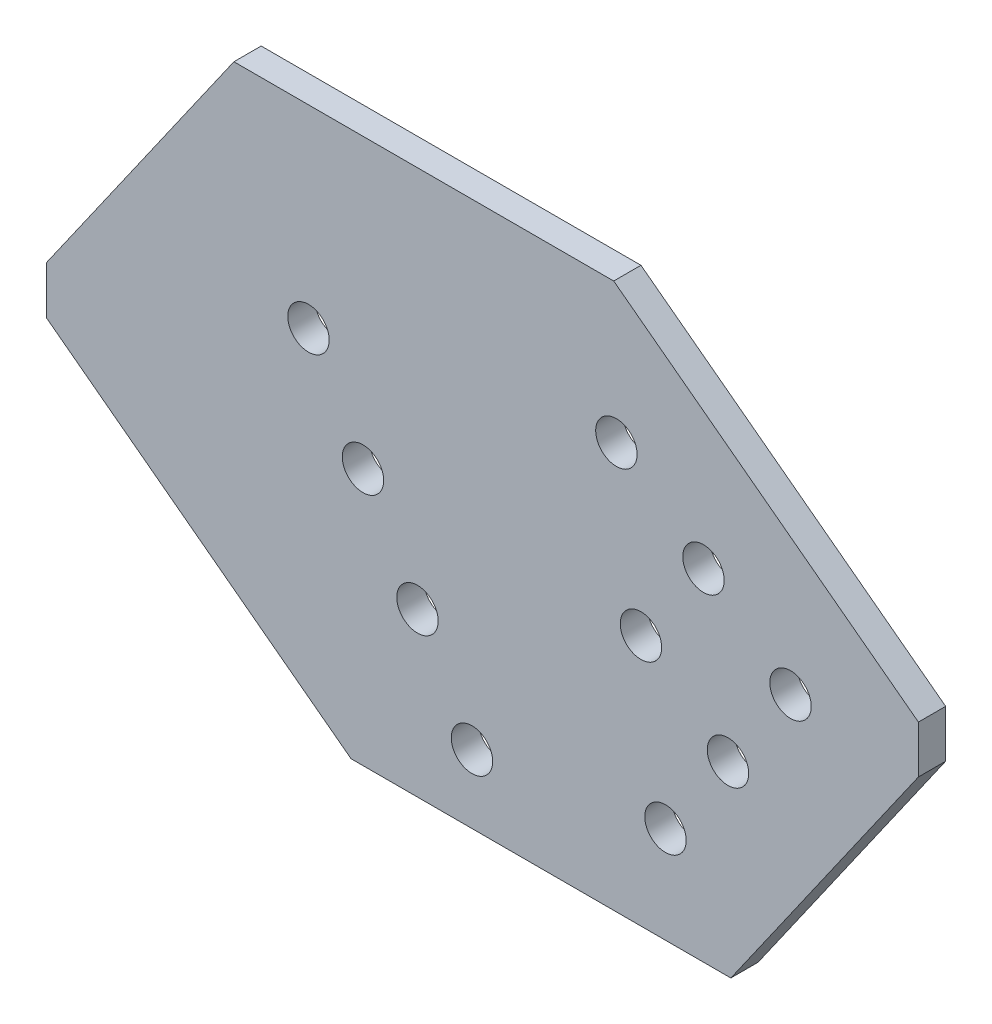
SolidWorks part; units mm, degrees
ref_plane "Front Plane" through (0, 0, 0) normal (0, 0, 1) x (1, 0, 0)
ref_plane "Top Plane" through (0, 0, 0) normal (0, 1, 0) x (1, 0, 0)
ref_plane "Right Plane" through (0, 0, 0) normal (1, 0, 0) x (0, 0, -1)
sketch "Sketch1" plane through (0, 0, 0) normal (0, 0, 1) x (1, 0, 0)
  line L1 (0, 0) -> (101.6, 0)
  line L2 (0, 0) -> (0, 63.5)
  line L3 (0, 63.5) -> (101.6, 63.5)
  line L4 (101.6, 0) -> (101.6, 63.5)
  dimension "D1" = 101.6
  dimension "D2" = 63.5
extrude "Boss-Extrude1" add sketch "Sketch1" along normal blind 3.175
sketch "Sketch2" plane through (0, 0, 3.175) normal (0, 0, 1) x (1, 0, 0)
  line L0 (101.6, 31.2097) -> (79.7467, 0)
  line L1 (101.6, 0) -> (101.6, 63.5) construction
  line L2 (0, 0) -> (101.6, 0) construction
  line L3 (101.6, 36.7493) -> (66.1007, 63.5)
  line L4 (101.6, 63.5) -> (0, 63.5) construction
  line L5 (66.1007, 63.5) -> (101.6, 63.5)
  line L6 (101.6, 63.5) -> (101.6, 36.7493)
  line L7 (101.6, 31.2097) -> (101.6, 0)
  line L8 (101.6, 0) -> (79.7467, 0)
  dimension "D1" = 55
  dimension "D2" = 37
  dimension "D3" = 38.1
  dimension "D4" = 44.45
extrude "Cut-Extrude1" cut sketch "Sketch2" against normal through all
sketch "Sketch3" plane through (0, 0, 3.175) normal (0, 0, 1) x (1, 0, 0)
  line L0 (21.8533, 63.5) -> (0, 32.2903)
  line L1 (66.1007, 63.5) -> (0, 63.5) construction
  line L2 (0, 63.5) -> (0, 0) construction
  line L3 (0, 32.2903) -> (0, 63.5)
  line L4 (0, 63.5) -> (21.8533, 63.5)
  line L5 (0, 0) -> (0, 26.7507)
  line L6 (0, 26.7507) -> (35.4993, 0)
  line L7 (0, 0) -> (79.7467, 0) construction
  line L8 (35.4993, 0) -> (0, 0)
  dimension "D1" = 55
  dimension "D2" = 38.1
  dimension "D3" = 44.45
  dimension "D4" = 37
extrude "Cut-Extrude2" cut sketch "Sketch3" against normal through all
sketch "Sketch4" plane through (0, 0, 3.175) normal (0, 0, 1) x (1, 0, 0)
  line L0 (26.7476, 47.5267) -> (55.9415, -3.0386) construction
  line L2 (35.4993, 0) -> (79.7467, 0) construction
  circle A0 centre (55.9415, -3.0386) radius 2.413 construction
  circle A1 centre (49.5915, 7.9599) radius 2.413
  circle A2 centre (43.2415, 18.9584) radius 2.413
  circle A3 centre (36.8915, 29.9569) radius 2.413
  circle A4 centre (30.5415, 40.9555) radius 2.413
  circle A5 centre (24.1915, 51.954) radius 2.413 construction
  dimension "D2" = 4.826
  dimension "D1" = 60
  dimension "D3" = 6
extrude "Cut-Extrude3" cut sketch "Sketch4" against normal through all
sketch "Sketch5" plane through (0, 0, 3.175) normal (0, 0, 1) x (1, 0, 0)
  line L0 (101.6, 31.2097) -> (79.7467, 0) construction
  line L1 (66.1007, 63.5) -> (101.6, 36.7493) construction
  line L2 (86.7014, 32.0741) -> (71.9652, 11.0285) construction
  line L3 (86.7014, 32.0741) -> (55.3467, 55.7016) construction
  circle A0 centre (86.7014, 32.0741) radius 2.413
  circle A2 centre (76.5587, 39.7171) radius 2.413
  circle A3 centre (66.4161, 47.3602) radius 2.413
  circle A4 centre (56.2734, 55.0032) radius 2.413 construction
  circle A5 centre (69.2743, 29.3139) radius 2.413
  circle A6 centre (59.1317, 36.957) radius 2.413 construction
  circle A7 centre (48.989, 44.6) radius 2.413 construction
  circle A8 centre (61.9899, 18.9107) radius 2.413 construction
  circle A9 centre (51.8472, 26.5537) radius 2.413 construction
  circle A10 centre (41.7046, 34.1968) radius 2.413 construction
  circle A11 centre (79.417, 21.6709) radius 2.413
  circle A12 centre (72.1326, 11.2676) radius 2.413
  dimension "D1" = 4.826
  dimension "D2" = 12.7
  dimension "D3" = 12.7
  dimension "D4" = 4
  dimension "D5" = 3
extrude "Cut-Extrude4" cut sketch "Sketch5" against normal through all
